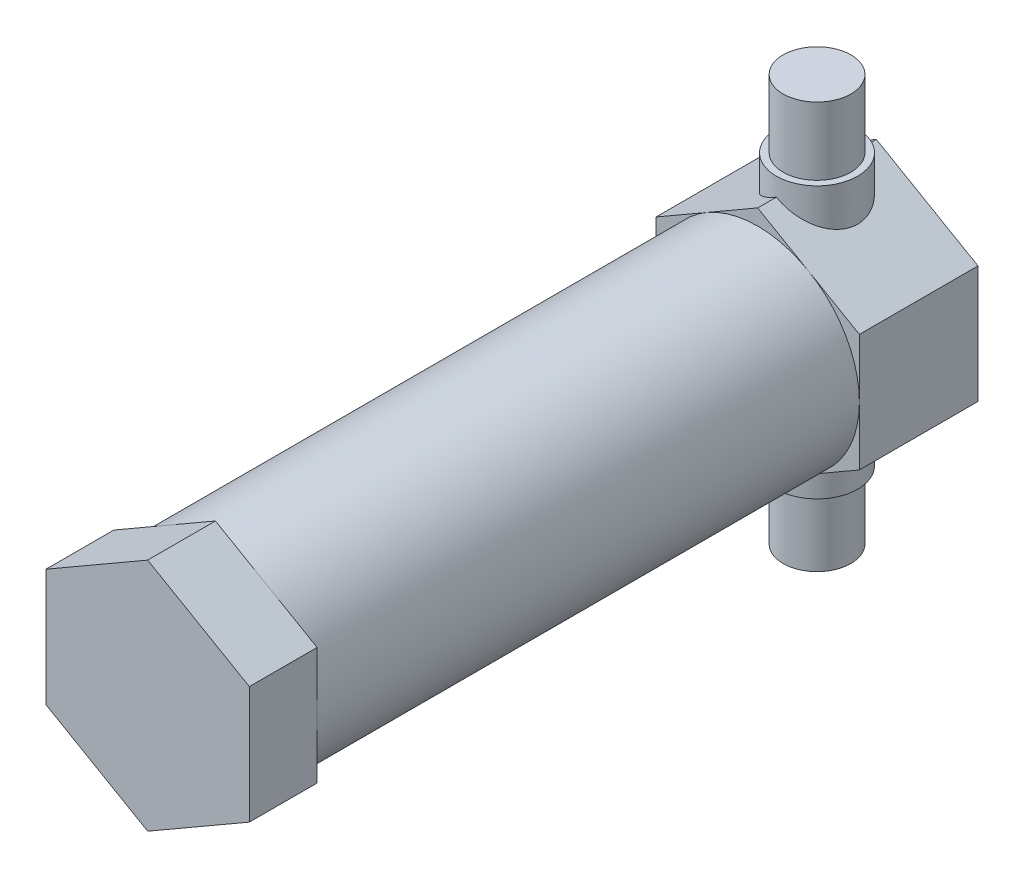
SolidWorks part; units mm, degrees
ref_plane "Front Plane" through (0, 0, 0) normal (0, 0, 1) x (1, 0, 0)
ref_plane "Top Plane" through (0, 0, 0) normal (0, 1, 0) x (1, 0, 0)
ref_plane "Right Plane" through (0, 0, 0) normal (1, 0, 0) x (0, 0, -1)
sketch "Sketch6" plane through (0, 0, 0) normal (0, 0, 1) x (1, 0, 0)
  circle A0 centre (0, 0) radius 9.525
  dimension "D1" = 19.05
extrude "Boss-Extrude5" add sketch "Sketch6" along normal blind 68.2625
sketch "Sketch7" plane through (0, 0, 68.2625) normal (0, 0, 1) x (1, 0, 0)
  line L1 (0, 10.9985) -> (-9.525, 5.4993)
  line L2 (-9.525, 5.4993) -> (-9.525, -5.4993)
  line L3 (-9.525, -5.4993) -> (0, -10.9985)
  line L4 (0, -10.9985) -> (9.525, -5.4993)
  line L5 (9.525, -5.4993) -> (9.525, 5.4993)
  line L6 (9.525, 5.4993) -> (0, 10.9985)
  circle A0 centre (0, 0) radius 9.525 construction
  circle A1 centre (0, 0) radius 9.525 construction
  point P11 (0, 0)
extrude "Boss-Extrude6" add sketch "Sketch7" against normal blind 6.35 contours L6 L1 L2 L3 L4 L5
sketch "Sketch8" plane through (0, 0, 0) normal (0, 0, -1) x (-1, 0, 0)
  line L0 (0, 10.9985) -> (4.7625, 8.2489) construction
  line L1 (0, 10.9985) -> (-9.525, 5.4993)
  line L2 (-9.525, 5.4993) -> (-9.525, -5.4993)
  line L3 (-9.525, -5.4993) -> (0, -10.9985)
  line L4 (0, -10.9985) -> (9.525, -5.4993)
  line L5 (9.525, -5.4993) -> (9.525, 5.4993)
  line L6 (9.525, 5.4993) -> (0, 10.9985)
  circle A0 centre (0, 0) radius 9.525 construction
extrude "Boss-Extrude7" add sketch "Sketch8" against normal blind 11.1125 contours L1 L2 L3 L4 L5 L6
sketch "Sketch9" plane through (0, 0, 0) normal (0, 1, 0) x (1, 0, 0)
  line L0 (0, -11.1125) -> (0, 0) construction
  circle A0 centre (0, -5.5562) radius 3.175
  dimension "D1" = 6.35
extrude "Boss-Extrude8" add sketch "Sketch9" along normal mid plane 38.1
sketch "Sketch11" plane through (0, 0, 0) normal (0, 1, 0) x (1, 0, 0)
  circle A0 centre (0, -5.5562) radius 3.81
  dimension "D1" = 7.62
extrude "Boss-Extrude9" add sketch "Sketch11" along normal mid plane 25.4
sketch "Sketch12" plane through (0, 0, 0) normal (0, 0, -1) x (-1, 0, 0)
  circle A0 centre (0, 0) radius 6.35
  dimension "D1" = 12.7
extrude "Cut-Extrude2" cut sketch "Sketch12" against normal blind 50.8
